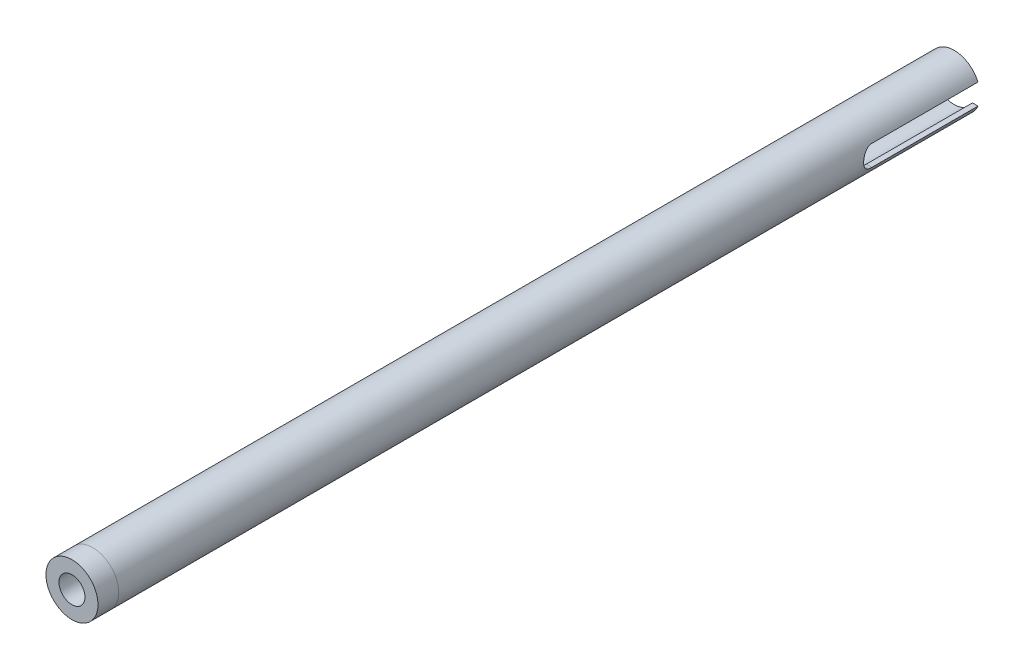
SolidWorks part; units mm, degrees
material "AISI 4130 Steel, annealed at 865C"
ref_plane "Front Plane" through (0, 0, 0) normal (0, 0, 1) x (1, 0, 0)
ref_plane "Top Plane" through (0, 0, 0) normal (0, 1, 0) x (1, 0, 0)
ref_plane "Right Plane" through (0, 0, 0) normal (1, 0, 0) x (0, 0, -1)
sketch "Axis" plane through (0, 0, 0) normal (0, 1, 0) x (1, 0, 0)
  line L0 (0, 0) -> (0, 269.2592) construction
  line L1 (0, 0) -> (0, -28.575) construction
  line L2 (0, 269.2592) -> (-7.9375, 269.2592) construction
  line L3 (0, 289.8013) -> (-10.3188, 263.0966) construction
  dimension "D1" = 28.575
  dimension "D2" = 7.9375
sketch "Sketch1" plane through (0, 0, 0) normal (0, 0, 1) x (1, 0, 0)
  line L0 (-7.9375, 0) -> (7.9375, 0) construction
  line L1 (-7.2748, 3.175) -> (7.2748, 3.175)
  line L2 (-7.2748, -3.175) -> (7.2748, -3.175)
  circle A0 centre (0, 0) radius 7.9375
  circle A1 centre (0, 0) radius 6.4135
  circle A2 centre (0, 0) radius 3.9688
  dimension "D1" = 15.875
  dimension "D3" = 7.9375
  dimension "D2" = 1.524
  dimension "D4" = 6.35
extrude "Threaded insert 1-1" add sketch "Sketch1" against normal blind 6.35 contours A2 L1 A1 | A1 L1 A0 | A2 L0 A1 L1 | A1 L0 A0 L1 | L0 A1 L2 A0 | L0 A2 L2 A1 | A2 L2 A1 | A1 L2 A0 | L0 A1 L2 A2 | L0 A0 L2 A1 | A0 L0 A1 L1 | A1 L0 A2 L1 region at (4.7887, 1.6543, 0) region at (4.7887, -1.6543, 0) region at (6.9234, 1.6163, 0) region at (6.9234, -1.6163, 0) region at (-4.7887, -1.6543, 0) region at (-4.7887, 1.6543, 0) region at (0, 4.6159, 0) region at (0, -4.6159, 0) region at (0, 6.5666, 0) region at (6.4237, -3.3281, 0) region at (-6.9234, -1.6163, 0) region at (-6.9234, 1.6163, 0)
extrude "Threaded insert 1-2" add sketch "Sketch1<3>" against normal blind 9.525 from surface contours A2 L1 A1 | A2 L0 A1 L1 | L0 A2 L2 A1 | A2 L2 A1 | L0 A1 L2 A2 | A1 L0 A2 L1 region at (4.7887, 1.6543, 0) region at (4.7887, -1.6543, 0) region at (-4.7887, -1.6543, 0) region at (-4.7887, 1.6543, 0) region at (0, 4.6159, 0) region at (0, -4.6159, 0) starting at face at (7.9375, 0, -6.35)
sketch "Sketch1<3>" plane through (0, 0, 0) normal (0, 0, 1) x (1, 0, 0) same geometry as "Sketch1"
extrude "A-arm tube" add sketch "Sketch1<4>" against normal up to vertex (269.2592 mm away) from surface separate body contours A1 L1 A0 | A1 L0 A0 L1 | L0 A1 L2 A0 | A1 L2 A0 | L0 A0 L2 A1 | A0 L0 A1 L1 region at (6.9234, 1.6163, 0) region at (6.9234, -1.6163, 0) region at (0, 6.5666, 0) region at (6.4237, -3.3281, 0) region at (-6.9234, -1.6163, 0) region at (-6.9234, 1.6163, 0) up to point (0, 0, -269.2592) starting at face at (6.4135, 0, -6.35)
sketch "Sketch1<4>" plane through (0, 0, 0) normal (0, 0, 1) x (1, 0, 0) same geometry as "Sketch1"
extrude "Apex slot" cut sketch "Sketch1<5>" along normal blind 35.56 from surface contours A0 L0 A1 L1 | L0 A0 L2 A1 | A1 L0 A0 L1 | L0 A1 L2 A0 region at (6.9234, 1.6163, 0) region at (6.9234, -1.6163, 0) region at (-6.9234, -1.6163, 0) region at (-6.9234, 1.6163, 0) starting at face at (6.4135, 0, -269.2592)
sketch "Sketch1<5>" plane through (0, 0, 0) normal (0, 0, 1) x (1, 0, 0) same geometry as "Sketch1"
fillet "Fillet1" radius 3.175 4 edges at (-6.4237, 3.175, -233.6992) (-6.4237, -3.175, -233.6992) (6.4237, -3.175, -233.6992) (6.4237, 3.175, -233.6992)
equation "\"tube diameter\"= 5 / 8"
equation "\"tube thickness\"= .06"
equation "\"apex thickness\"= .25"
equation "\"tube slot\"= 1.4"
equation "\"D1@Sketch1\"=\"tube diameter\""
equation "\"D2@Sketch1\"=\"tube thickness\""
equation "\"threaded insert hole\"= .3125"
equation "\"D3@Sketch1\"=\"threaded insert hole\""
equation "\"D4@Sketch1\"=\"apex thickness\""
equation "\"D1@Apex slot\" = \"tube slot\""
equation "\"D1@Fillet1\"=\"apex thickness\"/2"
